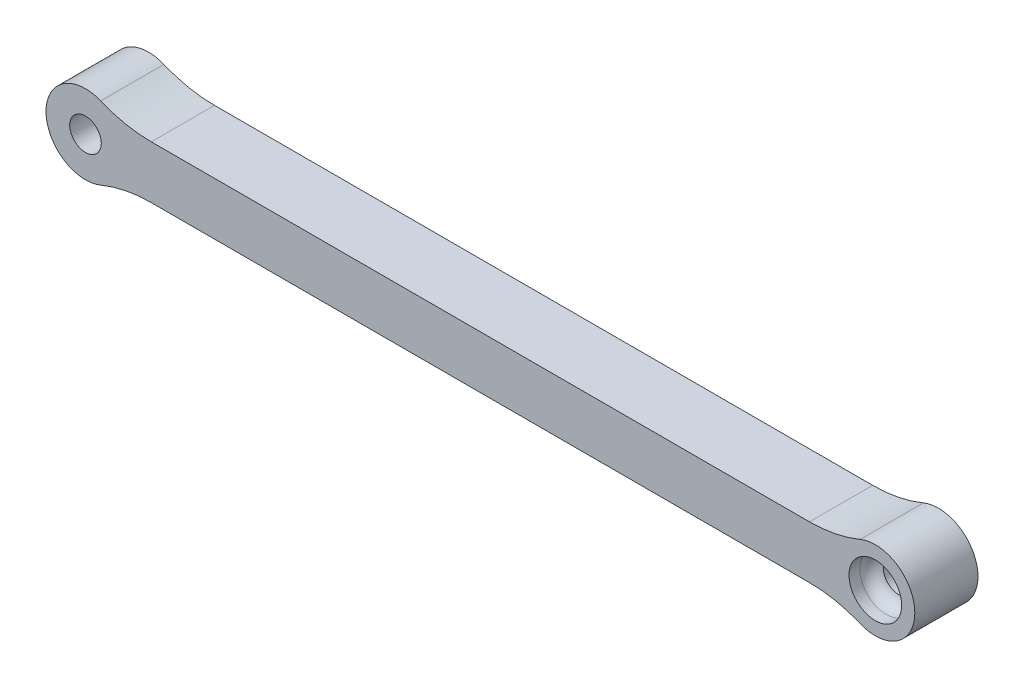
SolidWorks part; units mm, degrees
ref_plane "Front Plane" through (0, 0, 0) normal (0, 0, 1) x (1, 0, 0)
ref_plane "Top Plane" through (0, 0, 0) normal (0, 1, 0) x (1, 0, 0)
ref_plane "Right Plane" through (0, 0, 0) normal (1, 0, 0) x (0, 0, -1)
sketch "Sketch1" plane through (0, 0, 0) normal (0, 0, 1) x (1, 0, 0)
  line L0 (0, 0) -> (60, 0) construction
  line L1 (55, 0) -> (-55, 0) construction
  line L2 (5, -2) -> (55, -2)
  line L3 (5, 2) -> (55, 2)
  line L4 (0, 2) -> (60, 2) construction
  line L5 (0, -2) -> (60, -2) construction
  circle A0 centre (0, 0) radius 1.2
  circle A1 centre (60, 0) radius 1.2
  arc A2 (1.1538, 2.7692) -> (1.1538, -2.7692) centre (0, 0) ccw
  arc A3 (58.8462, -2.7692) -> (58.8462, 2.7692) centre (60, 0) ccw
  arc A4 (5, 2) -> (1.1538, 2.7692) centre (5, 12) cw
  arc A5 (5, -2) -> (1.1538, -2.7692) centre (5, -12) ccw
  arc A6 (55, 2) -> (58.8462, 2.7692) centre (55, 12) ccw
  arc A7 (55, -2) -> (58.8462, -2.7692) centre (55, -12) cw
  dimension "D1" = 2
  dimension "D3" = 10
  dimension "D4" = 10
  dimension "D5" = 10
  dimension "D6" = 10
  dimension "D2" = 2
extrude "Boss-Extrude1" add sketch "Sketch1" along normal blind 4.8
sketch "Sketch2" plane through (0, 0, 4.8) normal (0, 0, 1) x (1, 0, 0)
  circle A0 centre (60, 0) radius 2
extrude "Cut-Extrude1" cut sketch "Sketch2" against normal blind 1.8
fillet "Fillet1" radius 1 1 edges at (62, 0, 3)
